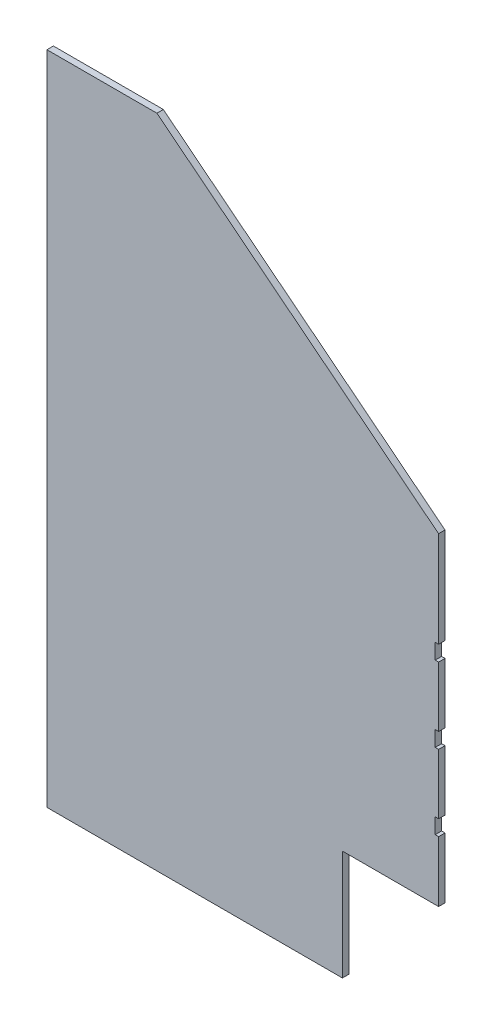
SolidWorks part; units mm, degrees
material "Pine"
ref_plane "Front Plane" through (0, 0, 0) normal (0, 0, 1) x (1, 0, 0)
ref_plane "Top Plane" through (0, 0, 0) normal (0, 1, 0) x (1, 0, 0)
ref_plane "Right Plane" through (0, 0, 0) normal (1, 0, 0) x (0, 0, -1)
sketch "Sketch1" plane through (0, 0, 0) normal (0, 0, 1) x (1, 0, 0)
  line L0 (96.4163, 530.1602) -> (617.1163, 117.4102)
  line L1 (-106.7837, 530.1602) -> (96.4163, 530.1602)
  line L2 (-106.7837, 530.1602) -> (-106.7837, -682.6898)
  line L3 (-106.7837, -682.6898) -> (439.3163, -682.6898)
  line L4 (617.1163, 117.4102) -> (617.1163, -479.4898)
  line L7 (617.1163, -479.4898) -> (439.3163, -479.4898)
  line L8 (439.3163, -682.6898) -> (439.3163, -479.4898)
  dimension "D1" = 177.8
  dimension "D2" = 203.2
  dimension "D3" = 1212.85
  dimension "D4" = 596.9
  dimension "D5" = 723.9
  dimension "D6" = 203.2
extrude "Boss-Extrude1" add sketch "Sketch1" along normal blind 11.9062
sketch "Sketch2" plane through (0, 0, 11.9062) normal (0, 0, 1) x (1, 0, 0)
  line L0 (617.1163, -479.4898) -> (617.1163, 117.4102) construction
  line L1 (617.1163, -367.5393) -> (610.7663, -367.5393)
  line L2 (617.1163, -367.5393) -> (617.1163, -338.9643)
  line L3 (617.1163, -338.9643) -> (610.7663, -338.9643)
  line L4 (610.7663, -367.5393) -> (610.7663, -338.9643)
  line L5 (439.3163, -479.4898) -> (617.1163, -479.4898) construction
  line L6 (617.1163, -227.8393) -> (610.7663, -227.8393)
  line L7 (617.1163, -227.8393) -> (617.1163, -199.2643)
  line L8 (617.1163, -199.2643) -> (610.7663, -199.2643)
  line L9 (610.7663, -227.8393) -> (610.7663, -199.2643)
  line L10 (617.1163, -88.1393) -> (610.7663, -88.1393)
  line L11 (617.1163, -88.1393) -> (617.1163, -59.5643)
  line L12 (617.1163, -59.5643) -> (610.7663, -59.5643)
  line L13 (610.7663, -88.1393) -> (610.7663, -59.5643)
  point P14 (610.7663, -353.2518)
  point P17 (610.7663, -213.5518)
  point P18 (610.7663, -73.8518)
  dimension "D1" = 28.575
  dimension "D2" = 6.35
  dimension "D3" = 126.238
  dimension "D4" = 265.938
  dimension "D5" = 405.638
extrude "Cut-Extrude1" cut sketch "Sketch2" against normal through all
